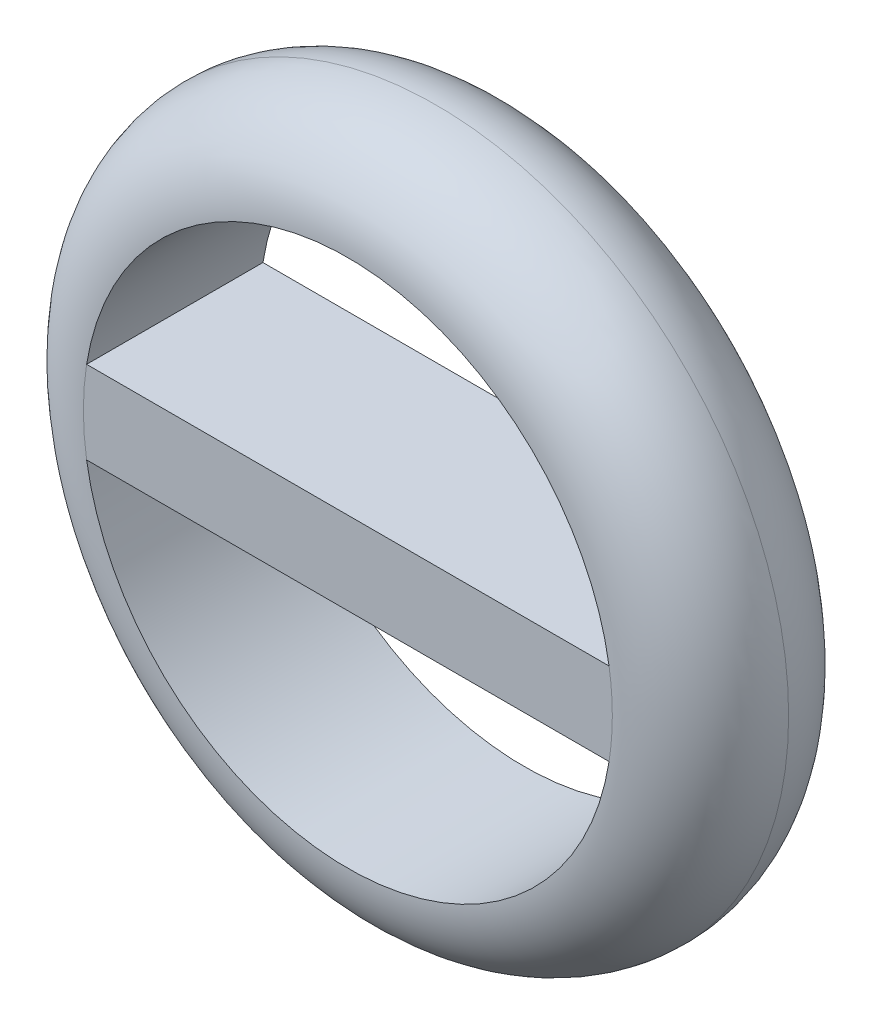
SolidWorks part; units mm, degrees
ref_plane "Front Plane" through (0, 0, 0) normal (0, 0, 1) x (1, 0, 0)
ref_plane "Top Plane" through (0, 0, 0) normal (0, 1, 0) x (1, 0, 0)
ref_plane "Right Plane" through (0, 0, 0) normal (1, 0, 0) x (0, 0, -1)
sketch "Sketch1" plane through (0, 0, 0) normal (0, 0, 1) x (1, 0, 0)
  line L1 (14.8153, 2.3467) -> (-14.8153, 2.3467)
  line L3 (14.8153, -2.3467) -> (-14.8153, -2.3467)
  arc A0 (-14.8153, -2.3467) -> (14.8153, -2.3467) centre (0, 0) ccw
  circle A1 centre (0, 0) radius 20
  arc A2 (14.8153, 2.3467) -> (-14.8153, 2.3467) centre (0, 0) ccw
  dimension "D1" = 30
extrude "Boss-Extrude1" add sketch "Sketch1" along normal blind 10 contours A1 A0 | L1 L3 region at (0, 0, 0)
fillet "Fillet1" radius 5 2 edges at (20, 0, 0) (20, 0, 10)
